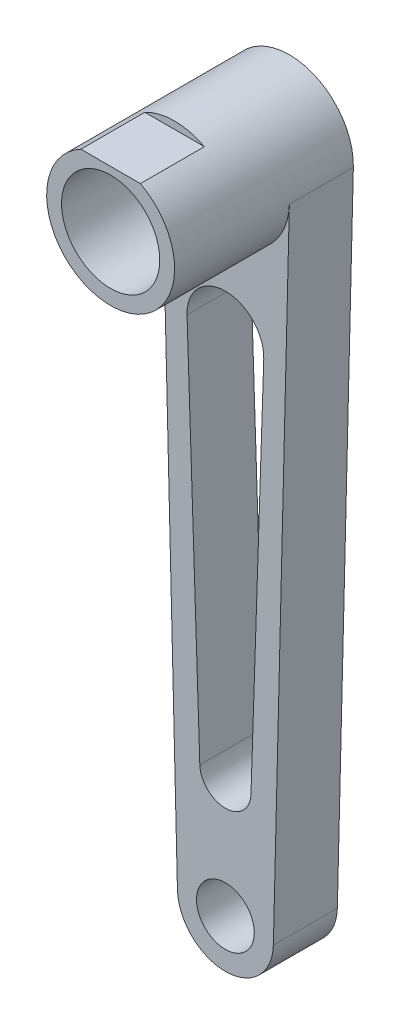
SolidWorks part; units mm, degrees
material "PEI"
ref_plane "Front Plane" through (0, 0, 0) normal (0, 0, 1) x (1, 0, 0)
ref_plane "Top Plane" through (0, 0, 0) normal (0, 1, 0) x (1, 0, 0)
ref_plane "Right Plane" through (0, 0, 0) normal (1, 0, 0) x (0, 0, -1)
sketch "Sketch1" plane through (0, 0, 0) normal (0, 0, 1) x (1, 0, 0)
  line L0 (-10.294, 11.8201) -> (-7.347, -107.9077)
  line L1 (0, -101.6) -> (0, 0) construction
  line L2 (7.347, -107.9067) -> (10.2653, 10.6574)
  line L3 (6.244, -15.7837) -> (3.867, -87.0546)
  line L4 (-6.2592, -15.3276) -> (-3.8401, -87.8596)
  circle A0 centre (0, 0) radius 10
  circle A1 centre (0, 0) radius 7.675
  circle A2 centre (0, -101.6) radius 7.5
  circle A3 centre (0, -101.6) radius 4.515
  circle A6 centre (0, -23) radius 6
  circle A7 centre (0, -83) radius 4
  dimension "D1" = 15.35
  dimension "D2" = 20
  dimension "D3" = 15
  dimension "D5" = 9.03
  dimension "D7" = 12
  dimension "D8" = 60
  dimension "D9" = 23
  dimension "D6" = 8
  dimension "D4" = 101.6
extrude "Boss-Extrude2" add sketch "Sketch1" along normal blind 10 contours L1 A2 L2 A0 | A2 L1 A0 L0 | A3 A2 region at (0, -11.0349, 0) region at (-0.0897, -94.3127, 0)
extrude "Boss-Extrude3" add sketch "Sketch1<6>" along normal blind 27.94 contours A0 A1 region at (-0.1196, 9.7164, 0)
sketch "Sketch1<6>" plane through (0, 0, 0) normal (0, 0, 1) x (1, 0, 0) same geometry as "Sketch1"
sketch "Sketch2" plane through (0, 0, 27.94) normal (0, 0, 1) x (1, 0, 0)
  line L0 (-10.0333, 8.85) -> (9.9921, 8.85)
  line L1 (9.9921, 8.85) -> (9.9921, 18.6582)
  line L2 (9.9921, 18.6582) -> (-10.0333, 18.6582)
  line L3 (-10.0333, 18.6582) -> (-10.0333, 8.85)
  circle A0 centre (0, 0) radius 10 construction
  point P3 (-0.0206, 8.85)
  dimension "D1" = 8.85
extrude "Cut-Extrude1" cut sketch "Sketch2" against normal blind 10
